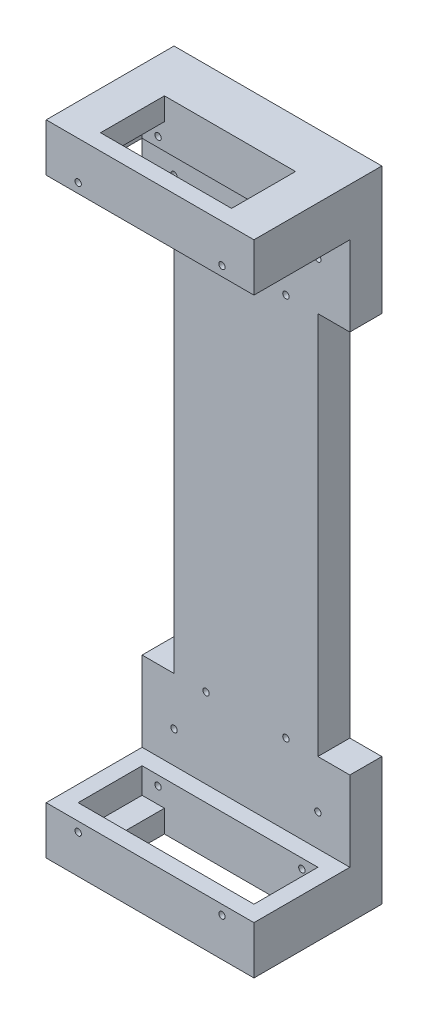
SolidWorks part; units mm, degrees
ref_plane "Plan de face" through (0, 0, 0) normal (0, 0, 1) x (1, 0, 0)
ref_plane "Plan de dessus" through (0, 0, 0) normal (0, 1, 0) x (1, 0, 0)
ref_plane "Plan de droite" through (0, 0, 0) normal (1, 0, 0) x (0, 0, -1)
sketch "Esquisse1" plane through (0, 0, 0) normal (0, 0, 1) x (1, 0, 0)
  line L0 (-10, -50) -> (-10, -40) construction
  line L1 (0, 0) -> (-65, 0)
  line L2 (0, 0) -> (0, -200)
  line L3 (0, -200) -> (-65, -200)
  line L4 (-65, 0) -> (-65, -200)
  line L5 (-55, -50) -> (-55, -40) construction
  line L6 (-10, -50) -> (-55, -50) construction
  line L7 (-10, -40) -> (0, -40) construction
  line L8 (-65, -40) -> (-55, -40) construction
  line L9 (-55, -150) -> (-10, -150) construction
  line L10 (-10, -150) -> (-10, -160) construction
  line L11 (-55, -150) -> (-55, -160) construction
  line L12 (-10, -160) -> (0, -160) construction
  line L13 (-55, -160) -> (-65, -160) construction
  circle A0 centre (-55, -25) radius 1
  circle A1 centre (-45, -40) radius 1
  circle A2 centre (-20, -40) radius 1
  circle A3 centre (-10, -25) radius 1
  circle A4 centre (-45, -160) radius 1
  circle A5 centre (-20, -160) radius 1
  circle A6 centre (-10, -175) radius 1
  circle A7 centre (-55, -175) radius 1
  dimension "D11" = 2
  dimension "D12" = 2
  dimension "D13" = 2
  dimension "D14" = 2
  dimension "D19" = 2
  dimension "D20" = 2
  dimension "D23" = 2
  dimension "D26" = 2
  dimension "D1" = 65
  dimension "D2" = 200
  dimension "D3" = 10
  dimension "D4" = 10
  dimension "D5" = 10
  dimension "D6" = 10
  dimension "D7" = 10
  dimension "D8" = 10
  dimension "D9" = 15
  dimension "D10" = 15
  dimension "D15" = 10
  dimension "D16" = 10
  dimension "D17" = 10
  dimension "D18" = 10
  dimension "D21" = 10
  dimension "D22" = 15
  dimension "D24" = 15
  dimension "D25" = 10
extrude "Boss.-Extru.1" add sketch "Esquisse1" along normal blind 10
sketch "Esquisse2" plane through (0, 0, 10) normal (0, 0, 1) x (1, 0, 0)
  line L5 (0, 0) -> (-65, 0)
  line L6 (0, 0) -> (0, -15)
  line L7 (0, -15) -> (-65, -15)
  line L8 (-65, 0) -> (-65, -15)
  line L9 (0, -200) -> (-65, -200)
  line L10 (0, -200) -> (0, -185)
  line L11 (0, -185) -> (-65, -185)
  line L12 (-65, -200) -> (-65, -185)
  point P0 (0, 0)
  dimension "D1" = 65
  dimension "D2" = 15
extrude "Boss.-Extru.2" add sketch "Esquisse2" along normal blind 30
sketch "Esquisse3" plane through (0, -200, 0) normal (0, -1, 0) x (1, 0, 0)
  line L5 (-53, 35) -> (-12, 35)
  line L6 (-53, 35) -> (-53, 15)
  line L7 (-53, 15) -> (-12, 15)
  line L8 (-12, 35) -> (-12, 15)
  line L13 (-65, 35) -> (-53, 35) construction
  line L17 (-65, 40) -> (-65, 0) construction
  line L18 (-53, 40) -> (-53, 35) construction
  line L19 (-65, 40) -> (0, 40) construction
  line L20 (-12, 40) -> (-12, 35) construction
  line L21 (0, 35) -> (-12, 35) construction
  line L22 (0, 40) -> (0, 0) construction
extrude "Enlèv. mat.-Extru.1" cut sketch "Esquisse3" against normal through all
sketch "Esquisse4" plane through (0, -15, 0) normal (0, -1, 0) x (1, 0, 0)
  line L8 (-12, 35) -> (-53, 35) construction
  line L9 (-60, 35) -> (-5, 35)
  line L10 (-60, 35) -> (-60, 15)
  line L11 (-60, 15) -> (-5, 15)
  line L12 (-5, 35) -> (-5, 15)
  line L13 (-53, 15) -> (-12, 15) construction
  line L14 (-65, 40) -> (-65, 0) construction
  line L15 (0, 40) -> (0, 0) construction
  dimension "D3" = 5
  dimension "D4" = 5
extrude "Enlèv. mat.-Extru.2" cut sketch "Esquisse4" against normal blind 8 and the other way blind 178
sketch "Esquisse5" plane through (0, 0, 40) normal (0, 0, 1) x (1, 0, 0)
  line L7 (-65, -188) -> (-55, -188)
  line L8 (-65, -185) -> (-65, -200) construction
  line L9 (-55, -188) -> (-55, -185)
  line L10 (0, -185) -> (-65, -185) construction
  line L11 (-10, -185) -> (-10, -188)
  line L12 (-10, -188) -> (0, -188)
  line L13 (0, -200) -> (0, -185) construction
  line L14 (-10, -12) -> (-10, -15)
  line L15 (-65, -15) -> (0, -15) construction
  line L16 (-10, -12) -> (0, -12)
  line L17 (0, -15) -> (0, 0) construction
  line L18 (-65, -12) -> (-55, -12)
  line L19 (-65, -185) -> (-65, -15) construction
  line L20 (-55, -12) -> (-55, -15)
  line L21 (-65, -15) -> (0, -15) construction
  circle A1 centre (-55, -12) radius 1
  circle A2 centre (-10, -12) radius 1
  circle A3 centre (-10, -188) radius 1
  circle A4 centre (-55, -188) radius 1
  dimension "D1" = 10
  dimension "D2" = 3
  dimension "D3" = 2
  dimension "D4" = 2
  dimension "D5" = 2
  dimension "D6" = 2
extrude "Enlèv. mat.-Extru.3" cut sketch "Esquisse5" against normal through all contours L7 A4 L9 | L11 A3 L12 | L12 A3 L11 | L9 A4 L7 | A1 | A2 region at (-55.4244, -187.5756, 40) region at (-54.8585, -188.1415, 40) region at (-9.5756, -187.5756, 40) region at (-10.1415, -188.1415, 40)
sketch "Esquisse6" plane through (0, 0, 10) normal (0, 0, 1) x (1, 0, 0)
  line L0 (-55, -40) -> (-10, -40)
  line L1 (-55, -40) -> (-55, -160)
  line L2 (-10, -40) -> (-10, -160)
  line L3 (-55, -160) -> (-10, -160)
  line L4 (0, -185) -> (-65, -185) construction
  line L5 (-65, -15) -> (0, -15) construction
  line L6 (-65, -15) -> (-65, -185) construction
  line L7 (0, -185) -> (0, -15) construction
  line L8 (-55, -40) -> (-65, -40)
  line L9 (-55, -40) -> (-55, -160)
  line L10 (-65, -40) -> (-65, -160)
  line L11 (-55, -160) -> (-65, -160)
  line L12 (-10, -160) -> (0, -160)
  line L13 (-10, -160) -> (-10, -40)
  line L14 (0, -160) -> (0, -40)
  line L15 (-10, -40) -> (0, -40)
  point P12 (-55, -159.2626)
  point P16 (-10, -39.6062)
  line M14 (0, -185) -> (0, -15)
  line M16 (-65, -15) -> (-65, -185)
  dimension "D1" = 25
  dimension "D2" = 25
  dimension "D3" = 10
  dimension "D4" = 10
extrude "Enlèv. mat.-Extru.4" cut sketch "Esquisse6" against normal blind 10 contours L11 L1 L8 M16 | L15 L2 L12 M14 region at (-60, -100, 10) region at (-5, -100, 10)
